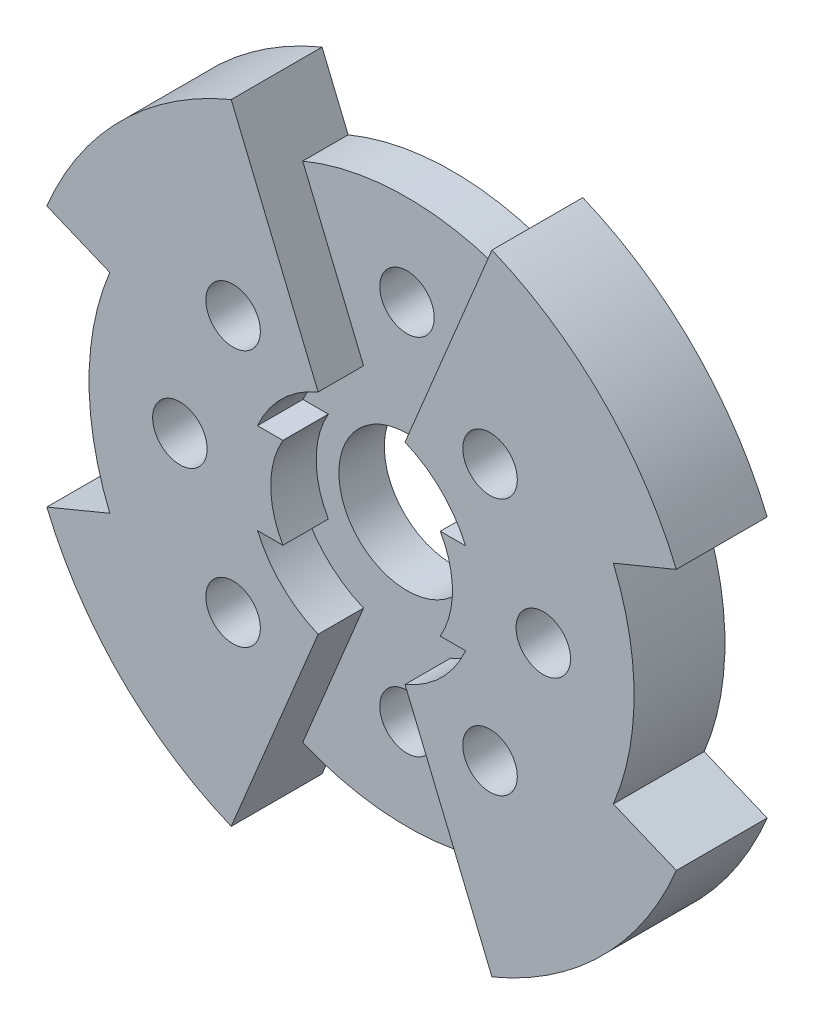
SolidWorks part; units mm, degrees
material "AISI 304"
ref_plane "Front Plane" through (0, 0, 0) normal (0, 0, 1) x (1, 0, 0)
ref_plane "Top Plane" through (0, 0, 0) normal (0, 1, 0) x (1, 0, 0)
ref_plane "Right Plane" through (0, 0, 0) normal (1, 0, 0) x (0, 0, -1)
sketch "Sketch1" plane through (0, 0, 0) normal (0, 0, 1) x (1, 0, 0)
  line L0 (17.3205, 10) -> (22.9129, 10)
  line L1 (9.5671, 23.097) -> (28.7013, 69.291)
  line L2 (69.291, 28.7013) -> (55.4328, 22.961)
  line L3 (0, 0) -> (0, 21.1327) construction
  line L4 (0.575, 0) -> (60.6897, 0) construction
  line L5 (0, 0) -> (69.291, 28.7013) construction
  line L6 (-69.291, 28.7013) -> (-55.4328, 22.961)
  line L7 (0, 0) -> (-69.291, 28.7013) construction
  line L8 (-9.5671, 23.097) -> (-28.7013, 69.291)
  line L9 (-17.3205, 10) -> (-22.9129, 10)
  line L10 (17.3205, -10) -> (22.9129, -10)
  line L11 (0, 0) -> (69.291, -28.7013) construction
  line L12 (69.291, -28.7013) -> (55.4328, -22.961)
  line L13 (9.5671, -23.097) -> (28.7013, -69.291)
  line L14 (0, 0) -> (-69.291, -28.7013) construction
  line L15 (-17.3205, -10) -> (-22.9129, -10)
  line L16 (-9.5671, -23.097) -> (-28.7013, -69.291)
  line L17 (-69.291, -28.7013) -> (-55.4328, -22.961)
  circle A0 centre (0, 0) radius 15
  arc A1 (22.9129, 10) -> (9.5671, 23.097) centre (0, 0) ccw
  arc A2 (28.7013, 69.291) -> (69.291, 28.7013) centre (0, 0) cw
  arc A3 (55.4328, 22.961) -> (55.4328, -22.961) centre (0, 0) cw
  arc A4 (17.3205, 10) -> (17.3205, -10) centre (0, 0) cw
  arc A6 (-55.4328, 22.961) -> (-55.4328, -22.961) centre (0, 0) ccw
  arc A7 (-28.7013, 69.291) -> (-69.291, 28.7013) centre (0, 0) ccw
  arc A8 (-17.3205, 10) -> (-17.3205, -10) centre (0, 0) ccw
  arc A9 (-22.9129, 10) -> (-9.5671, 23.097) centre (0, 0) cw
  arc A10 (28.7013, -69.291) -> (69.291, -28.7013) centre (0, 0) ccw
  arc A11 (22.9129, -10) -> (9.5671, -23.097) centre (0, 0) cw
  arc A12 (22.961, 55.4328) -> (-22.961, 55.4328) centre (0, 0) ccw
  arc A13 (-22.9129, -10) -> (-9.5671, -23.097) centre (0, 0) ccw
  arc A14 (-28.7013, -69.291) -> (-69.291, -28.7013) centre (0, 0) cw
  circle A15 centre (0, 40) radius 6
  circle A16 centre (28.2843, 28.2843) radius 6
  circle A17 centre (40, 0) radius 6
  circle A18 centre (28.2843, -28.2843) radius 6
  circle A19 centre (0, -40) radius 6
  circle A20 centre (-28.2843, -28.2843) radius 6
  circle A21 centre (-40, 0) radius 6
  circle A22 centre (-28.2843, 28.2843) radius 6
  arc A23 (22.961, -55.4328) -> (-22.961, -55.4328) centre (0, 0) cw
  dimension "D1" = 30
  dimension "D2" = 20
  dimension "D3" = 25
  dimension "D4" = 75
  dimension "D5" = 60
  dimension "D11" = 12
  dimension "D6" = 10
  dimension "D7" = 22.5
  dimension "D8" = 22.5
  dimension "D10" = 40
  dimension "D12" = 40
  dimension "D9" = 8
extrude "Boss-Extrude1" add sketch "Sketch1" along normal blind 20 contours L10 A11 L13 A10 L12 A3 L2 A2 L1 A1 L0 A4 A18 A17 A16 | A14 L16 A13 L15 A8 L9 A9 L8 A7 L6 A6 L17 A22 A21 A20 region at (20.1167, 8.491, 0) region at (-17.6582, 38.6874, 0)
extrude "Boss-Extrude2" add sketch "Sketch1<3>" along normal blind 10 contours L15 A13 L16 L13 A11 L10 A4 L0 A1 L1 L8 A9 L9 A8 A19 A15 A0 region at (18.7151, 0, 0)
sketch "Sketch1<3>" plane through (0, 0, 0) normal (0, 0, 1) x (1, 0, 0) same geometry as "Sketch1"
